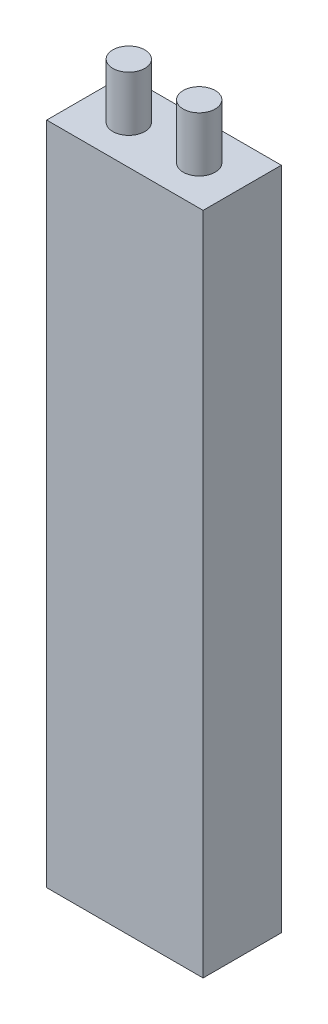
SolidWorks part; units mm, degrees
ref_plane "Front Plane" through (0, 0, 0) normal (0, 0, 1) x (1, 0, 0)
ref_plane "Top Plane" through (0, 0, 0) normal (0, 1, 0) x (1, 0, 0)
ref_plane "Right Plane" through (0, 0, 0) normal (1, 0, 0) x (0, 0, -1)
sketch "Sketch1" plane through (0, 0, 0) normal (0, 1, 0) x (1, 0, 0)
  line L0 (-25.4, 0) -> (25.4, 0)
  line L1 (-25.4, 0) -> (-25.4, 25.4)
  line L2 (-25.4, 25.4) -> (25.4, 25.4)
  line L3 (25.4, 25.4) -> (25.4, 0)
extrude "Boss-Extrude1" add sketch "Sketch1" along normal blind 215.9
sketch "Sketch2" plane through (0, 215.9, 0) normal (0, 1, 0) x (1, 0, 0)
  line L0 (0, 25.4) -> (0, 0) construction
  line L1 (25.4, 25.4) -> (-25.4, 25.4) construction
  line L2 (0, 12.7) -> (11.43, 12.7) construction
  line L3 (0, 12.7) -> (-11.43, 12.7) construction
  circle A0 centre (-11.43, 12.7) radius 5.207
  circle A1 centre (11.43, 12.7) radius 5.207
  dimension "D1" = 10.414
  dimension "D2" = 10.414
extrude "Boss-Extrude2" add sketch "Sketch2" along normal blind 17.78
sketch "Sketch3" plane through (0, 0, 0) normal (0, -1, 0) x (-1, 0, 0)
  line L0 (0, 0) -> (0, 25.4) construction
  line L1 (-25.4, 25.4) -> (25.4, 25.4) construction
  line L2 (0, 12.7) -> (-11.43, 12.7) construction
  line L3 (0, 12.7) -> (11.43, 12.7) construction
  circle A0 centre (11.43, 12.7) radius 5.207
  circle A1 centre (-11.43, 12.7) radius 5.207
  dimension "D1" = 10.414
  dimension "D2" = 10.414
extrude "Cut-Extrude1" cut sketch "Sketch3" against normal blind 17.78
